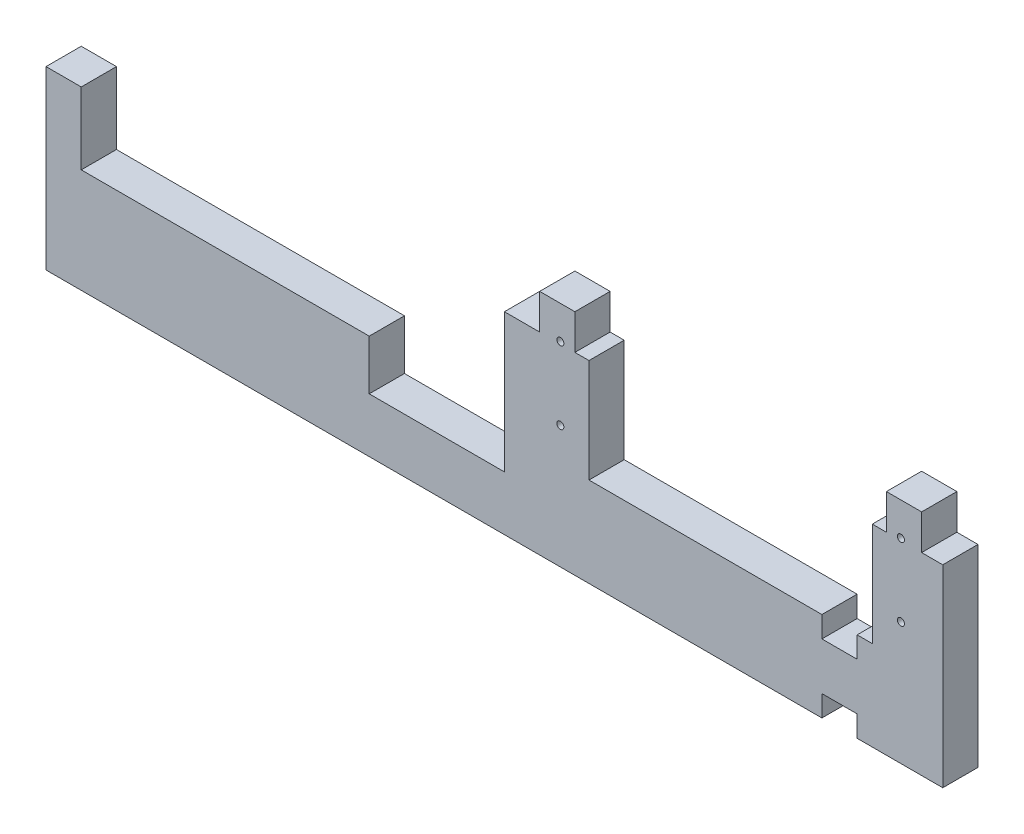
SolidWorks part; units mm, degrees
material "Balsa"
ref_plane "Plan de face" through (0, 0, 0) normal (0, 0, 1) x (1, 0, 0)
ref_plane "Plan de dessus" through (0, 0, 0) normal (0, 1, 0) x (1, 0, 0)
ref_plane "Plan de droite" through (0, 0, 0) normal (1, 0, 0) x (0, 0, -1)
sketch "Esquisse1" plane through (0, 0, 0) normal (0, 0, 1) x (1, 0, 0)
  line L0 (-40.2, 0) -> (-40.2, -19.685)
  line L1 (-40.2, -19.685) -> (0, -19.685)
  line L2 (0, -19.685) -> (0, 0)
  line L3 (0, 0) -> (10, 0)
  line L4 (10, 0) -> (10, -32.4016)
  line L5 (10, -32.4016) -> (-117.2486, -32.4016)
  line L6 (-52.2, -24.685) -> (-52.2, 0)
  line L7 (-52.2, 0) -> (-40.2, 0)
  line L8 (-117.2486, -32.4016) -> (-117.2486, -7.4016)
  line L10 (-71.3842, -17.5925) -> (-71.3842, -24.685)
  line L11 (-71.3842, -24.685) -> (-52.2, -24.685)
  line L12 (-117.2486, -7.4016) -> (-112.247, -7.4016)
  line L13 (-112.247, -7.4016) -> (-112.247, -17.5925)
  line L14 (-112.247, -17.5925) -> (-71.3842, -17.5925)
  dimension "D1" = 19.685
  dimension "D2" = 40.2
  dimension "D3" = 12
  dimension "D4" = 32.4016
  dimension "D5" = 10
  dimension "D6" = 24.685
  dimension "D7" = 17.5925
extrude "Boss.-Extru.1" add sketch "Esquisse1" along normal blind 5
sketch "Esquisse2" plane through (0, 0, 0) normal (0, 0, -1) x (-1, 0, 0)
  line L1 (7.15, -19.685) -> (2.15, -19.685)
  line L2 (7.15, -19.685) -> (7.15, -22.685)
  line L3 (7.15, -22.685) -> (2.15, -22.685)
  line L4 (2.15, -19.685) -> (2.15, -22.685)
  line L7 (7.15, -29.4016) -> (2.15, -29.4016)
  line L8 (7.15, -29.4016) -> (7.15, -32.4016)
  line L9 (7.15, -32.4016) -> (2.15, -32.4016)
  line L10 (2.15, -29.4016) -> (2.15, -32.4016)
  line L11 (-10, 0) -> (-7, 0)
  line L12 (-10, 0) -> (-10, -5)
  line L13 (-10, -5) -> (-7, -5)
  line L14 (-7, 0) -> (-7, -5)
  line L15 (52.2, 0) -> (52.2, -24.685) construction
  line L16 (0, 0) -> (-2, 0)
  line L17 (0, 0) -> (0, -5)
  line L18 (0, -5) -> (-2, -5)
  line L19 (-2, 0) -> (-2, -5)
  line L20 (40.2, 0) -> (42.2, 0)
  line L21 (40.2, 0) -> (40.2, -5)
  line L22 (40.2, -5) -> (42.2, -5)
  line L23 (42.2, 0) -> (42.2, -5)
  line L24 (52.2, -5) -> (47.2, -5)
  line L25 (52.2, -5) -> (52.2, 0)
  line L26 (52.2, 0) -> (47.2, 0)
  line L27 (47.2, -5) -> (47.2, 0)
  dimension "D1" = 19.685
  dimension "D2" = 6.7166
  dimension "D3" = 3
  dimension "D4" = 3
  dimension "D5" = 5
  dimension "D6" = 2.15
  dimension "D7" = 5
  dimension "D8" = 3
  dimension "D9" = 2
  dimension "D10" = 5
  dimension "D11" = 2
  dimension "D12" = 5
  dimension "D13" = 5
extrude "Créneaux -" cut sketch "Esquisse2" against normal blind 5
sketch "Esquisse3" plane through (0, 0, 0) normal (0, 0, -1) x (-1, 0, 0)
  line L0 (-10, -32.4016) -> (-10, -5) construction
  line L1 (-7, 0) -> (-2, 0) construction
  line L2 (40.2, -19.685) -> (40.2, -5) construction
  line L3 (42.2, 0) -> (47.2, 0) construction
  circle A0 centre (-4.064, -14.986) radius 0.5
  circle A1 centre (-4.064, -4.699) radius 0.5
  circle A2 centre (44.264, -14.986) radius 0.5
  circle A3 centre (44.264, -4.699) radius 0.5
  dimension "D1" = 1
  dimension "D2" = 1
  dimension "D7" = 1
  dimension "D8" = 1
  dimension "D3" = 10.287
  dimension "D4" = 5.936
  dimension "D5" = 5.936
  dimension "D6" = 4.699
  dimension "D9" = 4.064
  dimension "D10" = 4.064
  dimension "D11" = 10.287
  dimension "D12" = 4.699
extrude "Perçages" cut sketch "Esquisse3" against normal blind 5
